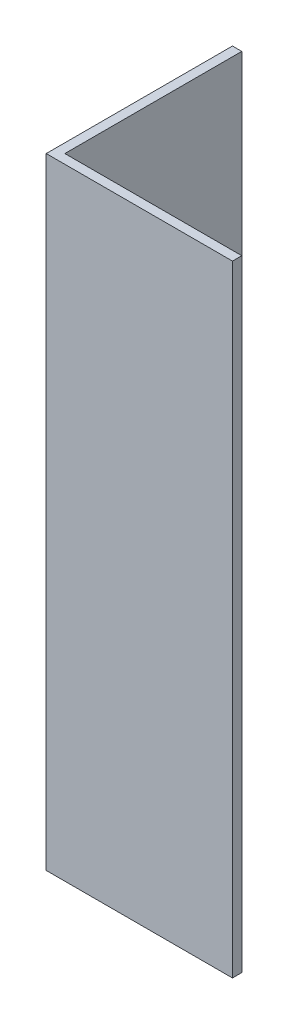
SolidWorks part; units mm, degrees
material "1060 Сплав"
ref_plane "Спереди" through (0, 0, 0) normal (0, 0, 1) x (1, 0, 0)
ref_plane "Сверху" through (0, 0, 0) normal (0, 1, 0) x (1, 0, 0)
ref_plane "Справа" through (0, 0, 0) normal (1, 0, 0) x (0, 0, -1)
sketch "Эскиз1" plane through (0, 0, 0) normal (0, 1, 0) x (1, 0, 0)
  line L0 (0, 0) -> (0, 15)
  line L1 (0, 15) -> (0.75, 15)
  line L2 (0.75, 15) -> (0.75, 0.75)
  line L3 (0.75, 0.75) -> (15, 0.75)
  line L4 (15, 0.75) -> (15, 0)
  line L5 (15, 0) -> (0, 0)
  dimension "D1" = 0.75
  dimension "D2" = 15
extrude "Бобышка-Вытянуть1" add sketch "Эскиз1" along normal blind 50
